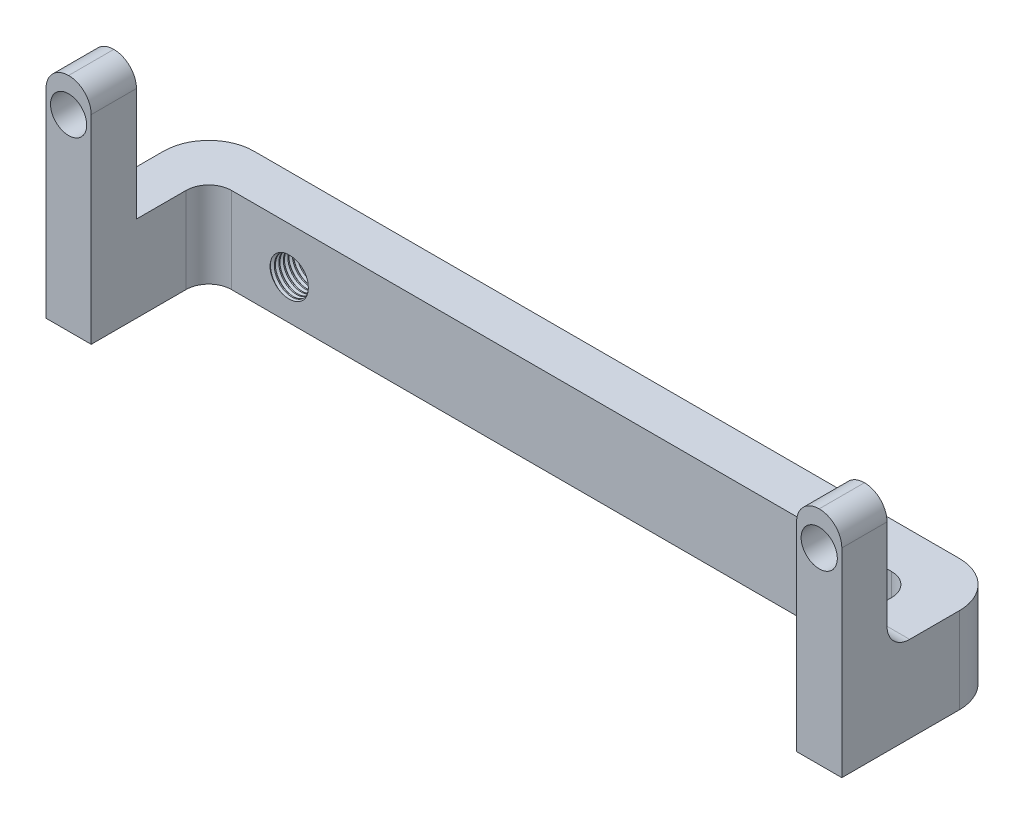
SolidWorks part; units mm, degrees
ref_plane "Front Plane" through (0, 0, 0) normal (0, 0, 1) x (1, 0, 0)
ref_plane "Top Plane" through (0, 0, 0) normal (0, 1, 0) x (1, 0, 0)
ref_plane "Right Plane" through (0, 0, 0) normal (1, 0, 0) x (0, 0, -1)
sketch "Sketch1" plane through (0, 0, 0) normal (0, 1, 0) x (1, 0, 0)
  line L0 (78, -10) -> (-78, -10)
  line L1 (-78, -10) -> (-78, -36)
  line L5 (-88, -10) -> (-88, 0)
  line L6 (-88, 0) -> (88, 0)
  line L8 (-88, -10) -> (-88, -36)
  line L9 (-88, -36) -> (-78, -36)
  line L10 (88, -36) -> (78, -36)
  line L11 (88, -18) -> (88, -36)
  line L12 (88, -18) -> (88, 0)
  line L13 (78, -10) -> (78, -36)
  point P0 (0, 0)
  dimension "D1" = 10
  dimension "D2" = 36
  dimension "D3" = 10
  dimension "D4" = 176
  dimension "D5" = 10
  dimension "D6" = 36
extrude "Boss-Extrude1" add sketch "Sketch1" along normal blind 25
sketch "Sketch2" plane through (0, 0, 36) normal (0, 0, 1) x (1, 0, 0)
  line L0 (78, 25) -> (88, 25) construction
  line L1 (78, 25) -> (88, 25)
  line L2 (78, 25) -> (78, 55)
  line L3 (78, 55) -> (88, 55)
  line L4 (88, 25) -> (88, 55)
  line L5 (0, 0) -> (0, 10.1221) construction
  line L6 (-88, 25) -> (-88, 55)
  line L7 (-78, 55) -> (-88, 55)
  line L8 (-78, 25) -> (-78, 55)
  line L9 (-78, 25) -> (-88, 25)
  dimension "D1" = 30
  dimension "D2" = 10
extrude "Boss-Extrude2" add sketch "Sketch2" against normal blind 10
fillet "Fillet1" radius 5 5 edges at (-88, 55, 31) (-78, 55, 31) (78, 55, 31) (88, 55, 31) (83, 25, 26)
sketch "Sketch3" plane through (0, 0, 0) normal (0, 0, -1) x (-1, 0, 0)
  line L1 (0, 0) -> (0, 12.1527) construction
  line L3 (-88, 25) -> (88, 25) construction
  circle A0 centre (-60, 15) radius 4
  circle A2 centre (60, 15) radius 4
  dimension "D1" = 8
  dimension "D2" = 10
  dimension "D3" = 60
sketch "Sketch4" plane through (0, 0, 26) normal (0, 0, -1) x (-1, 0, 0)
  line L1 (0, 0) -> (0, 8.6848) construction
  circle A0 centre (-83, 47.5) radius 4
  circle A1 centre (83, 47.5) radius 4
  dimension "D1" = 8
  dimension "D2" = 83
extrude "Cut-Extrude2" cut sketch "Sketch4" against normal blind 10
fillet "Fillet2" radius 10 2 edges at (-88, 12.5, 0) (88, 12.5, 0)
extrude "Cut-Extrude3" cut sketch "Sketch3" against normal up to next
thread "Thread1" pitch 1 method cut profile "Thread Profile1" start angle 0, offset 1, length 0, pitch 1, diameter 8
ref_plane "Plane1" through (64, 15, -1) normal (0, -1, 0) x (1, 0, 0)
sketch "Thread Profile1" plane through (64, 15, -1) normal (0, -1, 0) x (1, 0, 0)
  line L0 (0, 0) -> (0, 1) construction
  line L1 (0, 0) -> (0.5413, 0.3125)
  line L2 (0.5413, 0.3125) -> (0.5413, 0.4375)
  line L3 (0.5413, 0.4375) -> (0, 0.75)
  line L4 (0.5413, 0.375) -> (0, 0.375) construction
  line L11 (0, 0) -> (0, 0.75)
  point P2 (0, 0)
  dimension "Pitch" = 1
  dimension "Profile_Angle" = 60
  dimension "Profile_Land" = 0.125
  dimension "Profile_Height" = 0.5413
thread "Thread2" pitch 1 method cut profile "Thread Profile2" start angle 0, offset 1, length 0, pitch 1, diameter 8
ref_plane "Plane2" through (-56, 15, -1) normal (0, -1, 0) x (1, 0, 0)
sketch "Thread Profile2" plane through (-56, 15, -1) normal (0, -1, 0) x (1, 0, 0)
  line L0 (0, 0) -> (0, 1) construction
  line L1 (0, 0) -> (0.5413, 0.3125)
  line L2 (0.5413, 0.3125) -> (0.5413, 0.4375)
  line L3 (0.5413, 0.4375) -> (0, 0.75)
  line L4 (0.5413, 0.375) -> (0, 0.375) construction
  line L11 (0, 0) -> (0, 0.75)
  point P2 (0, 0)
  dimension "Pitch" = 1
  dimension "Profile_Angle" = 60
  dimension "Profile_Land" = 0.125
  dimension "Profile_Height" = 0.5413
fillet "Fillet3" radius 5 2 edges at (78, 12.5, 10) (-78, 12.5, 10)
sketch "Sketch5" plane through (0, 0, 0) normal (0, 0, -1) x (-1, 0, 0)
  line L0 (88, 25) -> (88, 0) construction
  line L1 (-88, 0) -> (88, 0)
  line L2 (-88, 0) -> (-88, 6)
  line L3 (-88, 6) -> (88, 6)
  line L4 (88, 0) -> (88, 6)
  dimension "D1" = 6
extrude "Cut-Extrude4" cut sketch "Sketch5" against normal up to surface (36 mm away) up to face at (-79, 47.5, 36)
